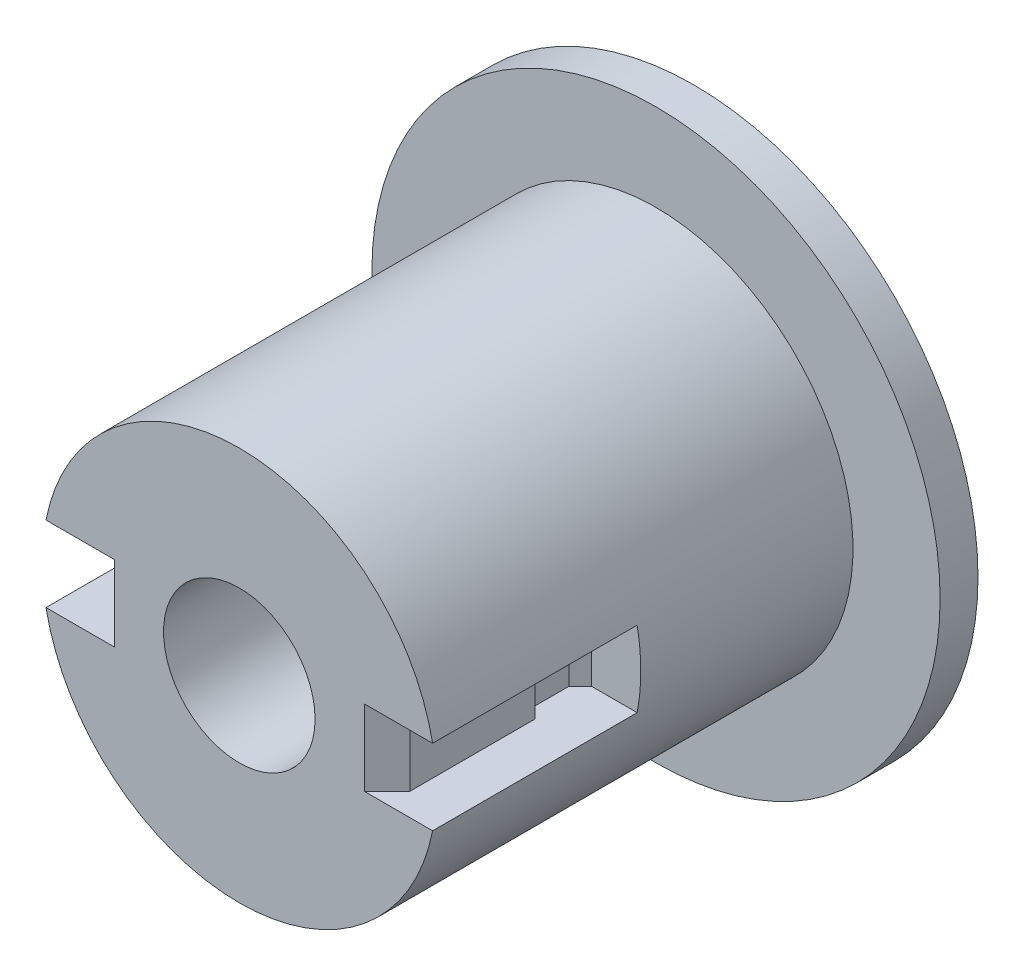
SolidWorks part; units mm, degrees
ref_plane "Front" through (0, 0, 0) normal (0, 0, 1) x (1, 0, 0)
ref_plane "Top" through (0, 0, 0) normal (0, 1, 0) x (1, 0, 0)
ref_plane "Right" through (0, 0, 0) normal (1, 0, 0) x (0, 0, -1)
sketch "Axle base sketch" plane through (0, 0, 0) normal (0, 0, 1) x (1, 0, 0)
  circle A0 centre (0, 0) radius 26
  dimension "D1" = 52
extrude "Axle" add sketch "Axle base sketch" along normal blind 55
sketch "Guard base sketch" plane through (0, 0, 0) normal (0, 0, -1) x (-1, 0, 0)
  circle A0 centre (0, 0) radius 37.5
  dimension "D1" = 75
extrude "Guard base" add sketch "Guard base sketch" along normal blind 5
sketch "Inner axle base sketch" plane through (0, 0, 55) normal (0, 0, 1) x (1, 0, 0)
  circle A0 centre (0, 0) radius 10
  dimension "D1" = 20
extrude "Inner axle hole" cut sketch "Inner axle base sketch" against normal through all
sketch "Coupling tooth base sketch" plane through (0, 0, 0) normal (0, 1, 0) x (1, 0, 0)
  line L0 (16.5, -55) -> (26, -55)
  line L1 (26, -55) -> (26, -28)
  line L2 (26, -55) -> (26, 0) construction
  line L3 (26, -28) -> (19.5, -28)
  line L5 (18, -34) -> (19.5, -35.5)
  line L6 (19.5, -35.5) -> (19.5, -52)
  line L7 (19.5, -52) -> (16.5, -55)
  line L9 (19.5, -28) -> (18, -29.5)
  line L10 (18, -29.5) -> (18, -34)
  dimension "D1" = 9.5
  dimension "D2" = 1.5
  dimension "D3" = 8
  dimension "D4" = 27
  dimension "D5" = 7.5
  dimension "D7" = 135
  dimension "D8" = 135
extrude "Coupling tooth room" cut sketch "Coupling tooth base sketch" against normal blind 5 and the other way blind 5 contours L9 L10 L5 L6 L7 L0 L1 L3 region at (22.4613, 0, 41.3333)
mirror "Coupling teeth" about plane through (0, 0, 0) normal (1, 0, 0) of "Coupling tooth room"
equation "\"53_55_spool_inner_diameter\"=53"
equation "\"D1@Axle base sketch\"=\"53_55_spool_inner_diameter\"-\"spool_inner_diameter_room\""
equation "\"large_inner_axle_diameter\"=20"
equation "\"small_inner_axle_diameter\"=17"
equation "\"guard_thickness\"=5"
equation "\"spool_inner_diameter_room\"=1"
equation "\"53_55_spool_thickness\"=55"
equation "\"53_55_guard_diameter\"=75"
equation "\"53_55_coupling_tooth_height\"=27"
equation "\"53_55_coupling_tooth_thickness_total\"=8"
equation "\"53_55_coupling_tooth_protrusion\"=1.5"
equation "\"53_55_coupling_tooth_head_height\"=7.5"
equation "\"53_55_coupling_tooth_depth\"=10"
equation "\"D1@Guard base sketch\"=\"53_55_guard_diameter\""
equation "\"D1@Guard base\"=\"guard_thickness\""
equation "\"D1@Axle\"=\"53_55_spool_thickness\""
equation "\"D1@Inner axle base sketch\" = \"large_inner_axle_diameter\""
equation "\"D4@Coupling tooth base sketch\"=\"53_55_coupling_tooth_height\""
equation "\"D3@Coupling tooth base sketch\"=\"53_55_coupling_tooth_thickness_total\""
equation "\"D5@Coupling tooth base sketch\"=\"53_55_coupling_tooth_head_height\""
equation "\"53_55_coupling_tooth_base_thickness\"=9.5"
equation "\"D1@Coupling tooth base sketch\"=\"53_55_coupling_tooth_base_thickness\""
equation "\"D2@Coupling tooth base sketch\"=\"53_55_coupling_tooth_protrusion\""
equation "\"D1@Coupling tooth room\"=\"53_55_coupling_tooth_depth\"/2"
equation "\"D2@Coupling tooth room\"=\"53_55_coupling_tooth_depth\"/2"
